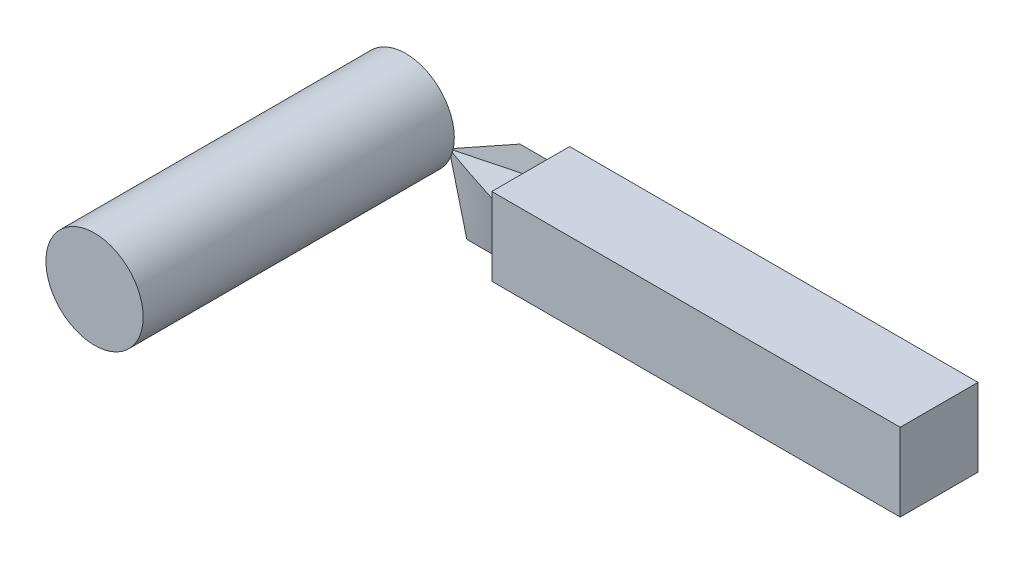
SolidWorks part; units mm, degrees
material "AISI Type A2 Tool Steel"
ref_plane "Front Plane" through (0, 0, 0) normal (0, 0, 1) x (1, 0, 0)
ref_plane "Top Plane" through (0, 0, 0) normal (0, 1, 0) x (1, 0, 0)
ref_plane "Right Plane" through (0, 0, 0) normal (1, 0, 0) x (0, 0, -1)
sketch "Sketch1" plane through (0, 0, 0) normal (1, 0, 0) x (0, 0, -1)
  line L1 (-10, -10) -> (10, -10)
  line L2 (-10, -10) -> (-10, 10)
  line L3 (-10, 10) -> (10, 10)
  line L4 (10, -10) -> (10, 10)
  line L5 (0, 10) -> (0, -10) construction
  line L6 (-10, 0) -> (10, 0) construction
  point P0 (0, 0)
  dimension "D1" = 20
extrude "Boss-Extrude1" add sketch "Sketch1" along normal blind 120
sketch "Sketch4" plane through (0, 10, 0) normal (0, 1, 0) x (1, 0, 0)
  line L0 (0, -5.9808) -> (15, -10)
  line L1 (0, 10) -> (0, -10) construction
  line L2 (120, -10) -> (0, -10) construction
  line L3 (15, -10) -> (0, -10)
  line L4 (0, -10) -> (0, 10)
  line L5 (0, 10) -> (2.2459, 10)
  line L6 (120, 10) -> (0, 10) construction
  line L7 (2.2459, 10) -> (0, -5.9808)
  line L9 (15, -10) -> (0, -10)
  line L10 (15, -10) -> (15, 10)
  line L11 (15, 10) -> (0, 10)
  line L12 (0, -10) -> (0, 10)
  line L13 (7.5, 10) -> (7.5, -10) construction
  line L14 (15, 0) -> (0, 0) construction
  point P72 (7.5, 0)
  line M5 (0, 10) -> (0, -10)
  line M6 (0, -10) -> (120, -10)
  line M8 (120, 10) -> (0, 10)
  dimension "D1" = 15
  dimension "D2" = 8
  dimension "D3" = 15
extrude "Cut-Extrude1" cut sketch "Sketch4" against normal blind 120 contours L7 M8 M5 | L0 M5 M6 region at (5, 10, 8.6603) region at (0.7486, 10, -4.6731)
sketch "Sketch5" plane through (0, 0, 10) normal (0, 0, 1) x (1, 0, 0)
  line L0 (0, 10) -> (15, 10)
  line L1 (0, 10) -> (15, 10) construction
  line L2 (15, 10) -> (15, 7.3551)
  line L3 (15, 7.3551) -> (0, 10)
  line L4 (0, -10) -> (2.4557, -10)
  line L5 (0, -10) -> (15, -10) construction
  line L6 (2.4557, -10) -> (0, 10)
  line L7 (0, -10) -> (0, 10) construction
  line L8 (0, 10) -> (0, -10)
  line L9 (15, -10) -> (15, 10) construction
  line M7 (15, 10) -> (15, -10)
  dimension "D1" = 10
  dimension "D2" = 7
extrude "Cut-Extrude2" cut sketch "Sketch5" against normal blind 120 contours L6 L8 L4 | L3 L0 M7 region at (10, 9.1184, 10) region at (0.8186, -3.3333, 10)
sketch "Sketch6" plane through (0, 0, 0) normal (1, 0, 0) x (0, 0, -1)
  line L0 (-5.9808, 10) -> (10, 10)
  line L1 (10, 10) -> (10, 4.1835)
  line L2 (10, 4.1835) -> (-5.9808, 10)
  line L6 (10, -8.2918) -> (10, 9.604) construction
  line L10 (-5.9808, 10) -> (-5.9808, -10)
  line L11 (10, -10) -> (-6.6388, -10) construction
  line L12 (-5.9808, -10) -> (-3.8787, -10)
  line L13 (-3.8787, -10) -> (-5.9808, 10)
  line L14 (-5.9808, 10) -> (-10, 10)
  line L15 (-5.9808, 10) -> (-5.9808, -10)
  line L16 (-5.9808, -10) -> (-10, -10)
  line L17 (-10, 10) -> (-10, -10)
  line L18 (-7.9904, -10) -> (-7.9904, 10) construction
  line L19 (-5.9808, 0) -> (-10, 0) construction
  point P125 (-7.9904, 0)
  dimension "D1" = 20
  dimension "D2" = 6
extrude "Cut-Extrude7" cut sketch "Sketch6" along normal blind 15 contours L2 L1 L0 region at (0, 8.0612, -4.6731)
sketch "Sketch7" plane through (0, 10, 0) normal (0, 1, 0) x (1, 0, 0)
  line L5 (15, -10) -> (0, -5.9808) construction
  line L6 (2.2459, 10) -> (0, -5.9808) construction
  line L7 (15, -10) -> (0.6837, -6.1639)
  line L8 (2.2459, 10) -> (0.0985, -5.2799)
  line L9 (2.2459, 10) -> (-4.8079, 10)
  line L10 (-4.8079, 10) -> (-4.8079, -10)
  line L11 (-4.8079, -10) -> (15, -10)
  arc A0 (0.6837, -6.1639) -> (0.0985, -5.2799) centre (0.8907, -5.3912) cw
  dimension "D1" = 0.8
extrude "Cut-Extrude9" cut sketch "Sketch7" against normal blind 28
extrude "Cut-Extrude10" cut sketch "Sketch6<9>" along normal blind 15 contours L10 L12 L13
sketch "Sketch6<9>" plane through (0, 0, 0) normal (1, 0, 0) x (0, 0, -1) same geometry as "Sketch6"
sketch "Sketch9" plane through (0, -10, 0) normal (0, -1, 0) x (1, 0, 0)
  line L0 (2.4557, -10) -> (2.4557, 3.8787)
  line L4 (2.4557, 3.8787) -> (15, 3.8787)
  line L5 (15, 3.8787) -> (15, -10)
  line L6 (120, -10) -> (2.4557, -10) construction
  line L7 (15, -10) -> (2.4557, -10)
extrude "Cut-Extrude12" cut sketch "Sketch6<12>" along normal blind 15 contours L14 L17 L16 L10 region at (0, 0, 7.9904)
sketch "Sketch6<12>" plane through (0, 0, 0) normal (1, 0, 0) x (0, 0, -1) same geometry as "Sketch6"
sketch "Sketch10" plane through (0, 10, 0) normal (0, 1, 0) x (1, 0, 0)
  line L0 (15, 10) -> (15, -10) construction
  line L1 (15, -10) -> (0, -10) construction
  line L2 (0, -10) -> (0, 10) construction
  line L3 (0, 10) -> (15, 10) construction
  line L4 (15, -10) -> (0, -5.9808)
  line L5 (0, -5.9808) -> (2.2459, 10)
  line L6 (2.2459, 10) -> (15, 10)
  line L7 (15, 10) -> (15, -10)
  line L8 (120, -10) -> (15, -10) construction
  dimension "D1" = 15
  dimension "D2" = 15
  dimension "D3" = 8
loft "Loft1" add profiles "Sketch10", "Sketch9"
sketch "Sketch12" plane through (0, 0, 10) normal (0, 0, 1) x (1, 0, 0)
  line L0 (0, 10) -> (15, 7.3551)
  line L1 (15, -10) -> (0, -10) construction
  line L2 (15, -10) -> (15, 10) construction
  line L3 (15, 10) -> (0, 10) construction
  line L4 (0, -10) -> (0, 10) construction
  line L5 (7.5, 10) -> (7.5, -10) construction
  line L6 (15, 0) -> (0, 0) construction
  line L7 (15, 7.3551) -> (15, 10)
  line L8 (15, 10) -> (0, 10)
  line L9 (0, -10) -> (2.4557, -10)
  line L10 (2.4557, -10) -> (0, 10)
  line L11 (0, 10) -> (0, -10)
  point P140 (7.5, 0)
  line M8 (15, 10) -> (15, -10)
  dimension "D1" = 20
  dimension "D2" = 15
  dimension "D3" = 10
  dimension "D4" = 7
extrude "Cut-Extrude14" cut sketch "Sketch12" against normal blind 24 contours L8 L0 M8 | L11 L9 L10 region at (10, 9.1184, 10)
sketch "Sketch13" plane through (0, 0, 0) normal (1, 0, 0) x (0, 0, -1)
  line L0 (-5.9808, 10) -> (10, 10)
  line L1 (10, 10) -> (10, 7.3551) construction
  line L2 (10, 10) -> (10, 4.1835)
  line L3 (10, 9.6032) -> (10, 4.1835) construction
  line L4 (10, 4.1835) -> (-5.9808, 10)
  dimension "D1" = 20
extrude "Cut-Extrude15" cut sketch "Sketch13" along normal blind 15
sketch "Sketch11" plane through (0, 10, 0) normal (0, 1, 0) x (1, 0, 0)
  line L0 (15, -10) -> (0, -5.9808) construction
  line L1 (15, -10) -> (0, -10) construction
  line L2 (15, -10) -> (15, 10.0215) construction
  line L3 (15, 10.0215) -> (0, 10.0215) construction
  line L4 (0, -10) -> (0, 10.0215) construction
  line L5 (7.5, 10.0215) -> (7.5, -10) construction
  line L6 (15, 0.0108) -> (0, 0.0108) construction
  line L7 (0, -5.9808) -> (2.249, 10.0215) construction
  line L8 (15, -10) -> (0.6837, -6.1639)
  line L10 (0.0985, -5.2799) -> (2.249, 10.0215)
  line L11 (2.249, 10.0215) -> (0, 10.0215)
  line L12 (0, 10.0215) -> (0, -10)
  line L13 (0, -10) -> (15, -10)
  arc A0 (0.6837, -6.1639) -> (0.0985, -5.2799) centre (0.8907, -5.3912) cw
  point P348 (7.5, 0.0108)
  dimension "D5" = 0.8
  dimension "D1" = 15
  dimension "D2" = 8
  dimension "D3" = 15
  dimension "D4" = 20.0215
extrude "Cut-Extrude13" cut sketch "Sketch11" against normal blind 24
sketch "Sketch14" plane through (1.8803, 0, 10) normal (0, 0, 1) x (1, 0, 0)
  circle A0 centre (-12.41, 13.7766) radius 12.5
  dimension "D1" = 25
extrude "Boss-Extrude2" add sketch "Sketch14" along normal blind 80 separate body
sketch "Sketch15" plane through (0, 10, 0) normal (0, 1, 0) x (1, 0, 0)
  line L0 (2.2459, 10) -> (0.0985, -5.2799) construction
  line L1 (2.2459, 10) -> (0.0985, -5.2799) construction
  line L2 (15, 10) -> (0, 10) construction
  line L3 (0, 10) -> (0, -10) construction
  line L5 (0, -10) -> (15, -10) construction
  arc A0 (0.2442, -5.8624) -> (0.5463, -6.1133) centre (0.8907, -5.3912) ccw construction
  arc A1 (0.0985, -5.2799) -> (0.2442, -5.8624) centre (0.8907, -5.3912) ccw construction
  arc A2 (0.2442, -5.8624) -> (0.5463, -6.1133) centre (0.8907, -5.3912) ccw construction
  arc A3 (0.0985, -5.2799) -> (0.2442, -5.8624) centre (0.8907, -5.3912) ccw construction
  spline S0 degree 3 poles (385.6765, -1951.7303) (-1106.6277, 2485.3855) (484.2684, -2337.0907) (491.8817, 1891.01) knots -63.603772 -63.603772 -63.603772 -63.603772 44.80424 44.80424 44.80424 44.80424 only from (0.5463, -6.1133) to (15, -9.1905) construction
  spline S1 degree 3 poles (0, -5.9808) (4.9696, -7.1914) (9.9709, -8.2667) (15, -9.1905) knots -0.038028 -0.038028 -0.038028 -0.038028 1 1 1 1 construction
  dimension "D1" = 20
ref_axis "Axis1" through (-10.5297, 13.7766, 90) along (0, 0, -1)
move or copy body "Body-Move/Copy1" bodies to move or copy 113 copy no translate (0, 0, -3.3892) parameters "D1"=0, "D2"=0, "D3"=3.3892
